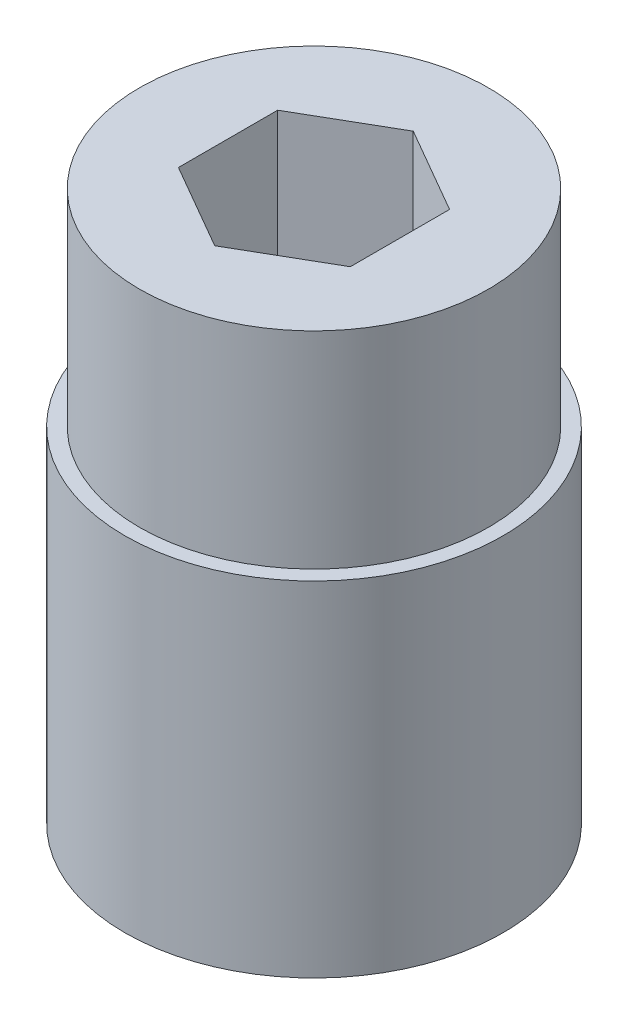
SolidWorks part; units mm, degrees
ref_plane "Front Plane" through (0, 0, 0) normal (0, 0, 1) x (1, 0, 0)
ref_plane "Top Plane" through (0, 0, 0) normal (0, 1, 0) x (1, 0, 0)
ref_plane "Right Plane" through (0, 0, 0) normal (1, 0, 0) x (0, 0, -1)
sketch "Sketch1" plane through (0, 0, 0) normal (0, 1, 0) x (1, 0, 0)
  circle A0 centre (0, 0) radius 7
  dimension "D1" = 14
extrude "Boss-Extrude1" add sketch "Sketch1" along normal blind 10
sketch "Sketch2" plane through (0, 10, 0) normal (0, 1, 0) x (1, 0, 0)
  circle A0 centre (0, 0) radius 5.075
  dimension "D1" = 10.15
extrude "Boss-Extrude2" add sketch "Sketch2" along normal blind 6
sketch "Sketch3" plane through (0, 16, 0) normal (0, 1, 0) x (1, 0, 0)
  line L1 (3.5, -1.4434) -> (3.5, 1.4434)
  line L2 (3.5, 1.4434) -> (1, 2.8868)
  line L3 (1, 2.8868) -> (-1.5, 1.4434)
  line L4 (-1.5, 1.4434) -> (-1.5, -1.4434)
  line L5 (-1.5, -1.4434) -> (1, -2.8868)
  line L6 (1, -2.8868) -> (3.5, -1.4434)
  circle A0 centre (1, 0) radius 2.5 construction
  dimension "D1" = 5
  dimension "D2" = 1
extrude "Cut-Extrude1" [suppressed] cut sketch "Sketch3" against normal through all
sketch "Sketch4" plane through (0, 16, 0) normal (0, 1, 0) x (1, 0, 0)
  line L1 (2.5, 1.4434) -> (0, 2.8868)
  line L2 (0, 2.8868) -> (-2.5, 1.4434)
  line L3 (-2.5, 1.4434) -> (-2.5, -1.4434)
  line L4 (-2.5, -1.4434) -> (0, -2.8868)
  line L5 (0, -2.8868) -> (2.5, -1.4434)
  line L6 (2.5, -1.4434) -> (2.5, 1.4434)
  circle A0 centre (0, 0) radius 2.5 construction
  dimension "D1" = 5
extrude "Cut-Extrude2" cut sketch "Sketch4" against normal through all
sketch "Sketch5" plane through (0, 10, 0) normal (0, 1, 0) x (1, 0, 0)
  circle A0 centre (0, 0) radius 5.5
  dimension "D1" = 11
extrude "Cut-Extrude3" cut sketch "Sketch5" against normal through all flip side to cut
equation "\"R_ROLL\"= 5mm"
equation "\"D_SUN\"= 80mm"
equation "\"NUM_ROLL\"= 16"
equation "\"RHO\"= 1mm"
equation "\"D_SHAFT\"= 15mm"
equation "\"D_OUTPUT\"= 40mm"
equation "\"NUM_OUT\"= 6"
equation "\"R_OUT_ROLL\"= 5mm"
